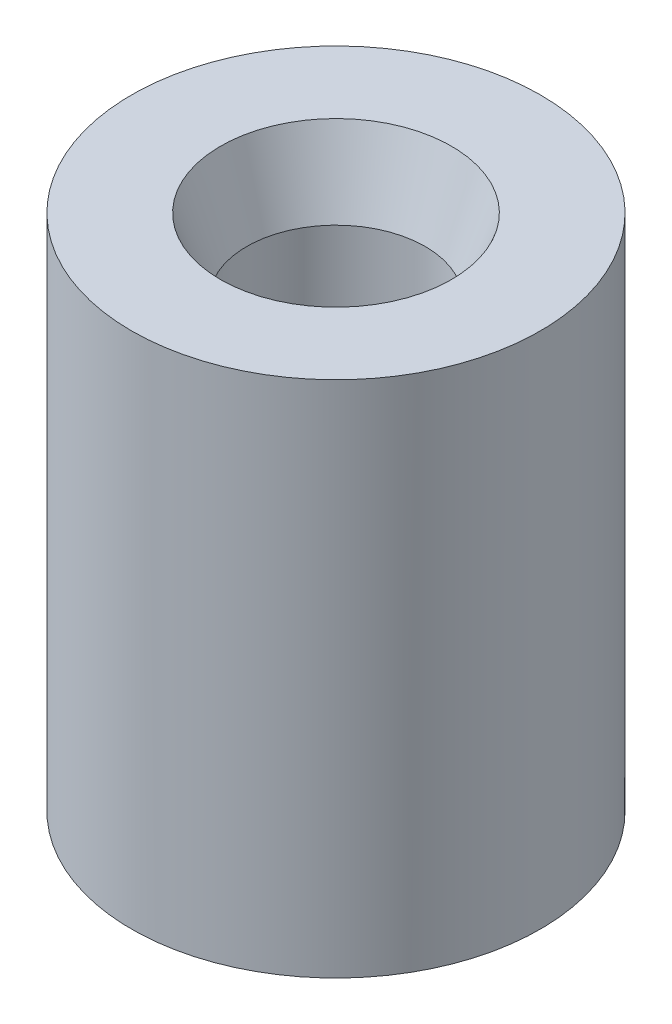
SolidWorks part; units mm, degrees
material "Nylon 101"
ref_plane "Front Plane" through (0, 0, 0) normal (0, 0, 1) x (1, 0, 0)
ref_plane "Top Plane" through (0, 0, 0) normal (0, 1, 0) x (1, 0, 0)
ref_plane "Right Plane" through (0, 0, 0) normal (1, 0, 0) x (0, 0, -1)
sketch "Sketch1" plane through (0, 0, 0) normal (0, 1, 0) x (1, 0, 0)
  circle A0 centre (0, 0) radius 5.842
  circle A1 centre (0, 0) radius 3.302
  dimension "D1" = 6.604
  dimension "D2" = 11.684
extrude "Boss-Extrude1" add sketch "Sketch1" along normal blind 2.1082
sketch "Sketch3" plane through (0, 0, 0) normal (0, 0, 1) x (1, 0, 0)
  line L0 (-3.302, 2.1082) -> (-2.5527, 0)
  line L1 (-2.5527, 0) -> (-3.302, 0)
  line L2 (-3.302, 0) -> (-3.302, 2.1082)
  line L3 (0, 0) -> (0, 2.1082) construction
  dimension "D1" = 2.5527
revolve "Revolve1" add sketch "Sketch3" angle 360 about L3
sketch "Sketch4" plane through (0, 0, 0) normal (0, -1, 0) x (1, 0, 0)
  circle A0 centre (0, 0) radius 2.5527 construction
  circle A1 centre (0, 0) radius 5.842
  circle A2 centre (0, 0) radius 5.842
  circle A3 centre (0, 0) radius 2.5527
  dimension "D1" = 0
extrude "Boss-Extrude2" add sketch "Sketch4" along normal blind 12.7
